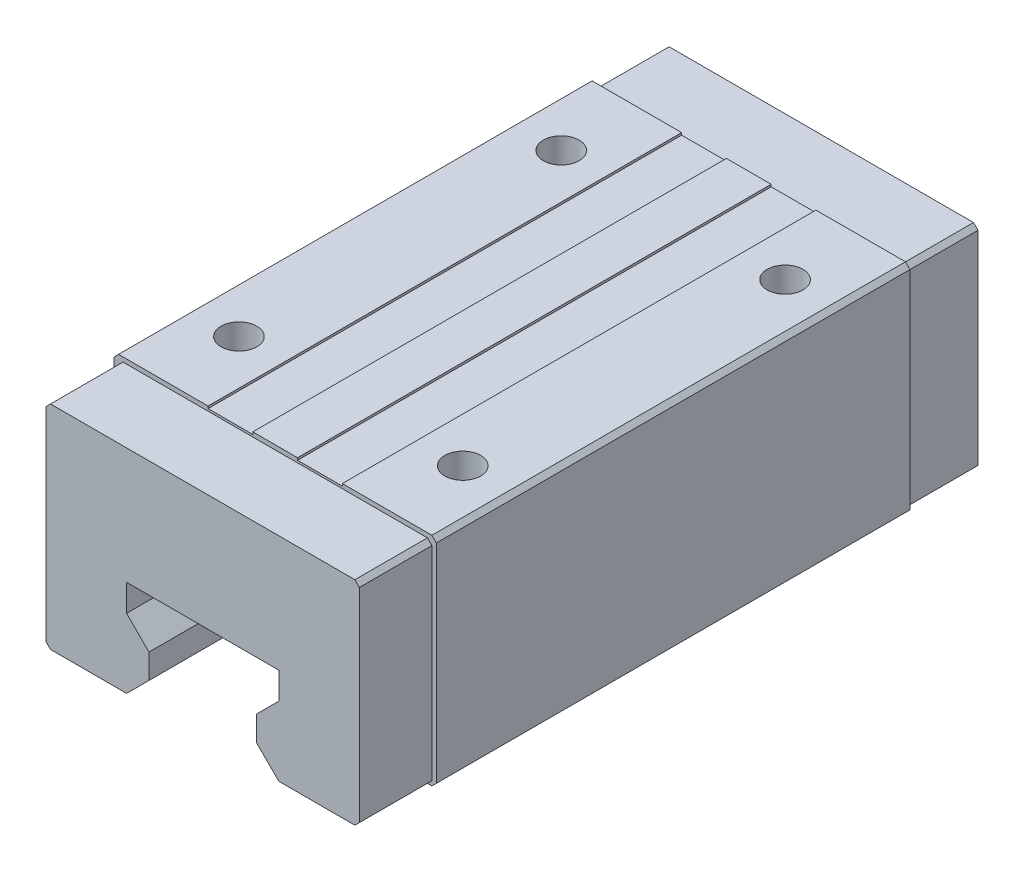
SolidWorks part; units mm, degrees
ref_plane "前视基准面" through (0, 0, 0) normal (0, 0, 1) x (1, 0, 0)
ref_plane "上视基准面" through (0, 0, 0) normal (0, 1, 0) x (1, 0, 0)
ref_plane "右视基准面" through (0, 0, 0) normal (1, 0, 0) x (0, 0, -1)
other "Configuration Table"
sketch "草图1" plane through (0, 0, 0) normal (0, 0, 1) x (1, 0, 0)
  line L0 (0, 55.4366) -> (0, -12.6403) construction
  line L1 (-35, 47.5) -> (35, 47.5)
  line L2 (35, 47.5) -> (35, 0)
  line L3 (35, 0) -> (17, 0)
  line L8 (17, 21.5) -> (-17, 21.5)
  line L13 (-35, 0) -> (-17, 0)
  line L14 (-35, 47.5) -> (-35, 0)
  line L15 (17, 15.5) -> (12, 10.5)
  line L16 (12, 10.5) -> (12, 5)
  line L17 (12, 5) -> (17, 0)
  line L19 (-12, 5) -> (-17, 0)
  line L20 (-12, 10.5) -> (-12, 5)
  line L21 (-17, 15.5) -> (-12, 10.5)
  line L22 (17, 15.5) -> (17, 21.5)
  line L23 (-17, 15.5) -> (-17, 21.5)
  point P19 (0, 21.5)
  point P25 (0, 47.5)
  dimension "D1" = 47.5
  dimension "D2" = 35
  dimension "D3" = 5
  dimension "D4" = 21.5
  dimension "D5" = 6
  dimension "D6" = 135
  dimension "D7" = 17
extrude "凸台-拉伸1" add sketch "草图1" along normal blind 138.2 contours L17 L3 L2 L1 L14 L13 L19 L20 L21 L23 L8 L22 L15 L16
ref_plane "基准面1" through (0, 0, 69.1) normal (0, 0, 1) x (1, 0, 0)
sketch "草图2" plane through (0, 0, 69.1) normal (0, 0, 1) x (1, 0, 0)
  line L0 (-36, 0) -> (-35, 0)
  line L1 (-35, 47.5) -> (-35, 0) construction
  line L2 (-36, 0) -> (-36, 48.5)
  line L3 (-36, 48.5) -> (-15, 48.5)
  line L4 (-35, 47.5) -> (35, 47.5) construction
  line L6 (-5, 48.5) -> (5, 48.5)
  line L7 (0, 0) -> (0, 45.4303) construction
  line L8 (36, 0) -> (35, 0)
  line L11 (-35, 47.5) -> (35, 47.5)
  line L12 (-35, 47.5) -> (-35, 0)
  line L13 (-15, 48.5) -> (-15, 48)
  line L14 (-15, 48) -> (-5, 48)
  line L15 (-5, 48) -> (-5, 48.5)
  line L16 (5, 48) -> (5, 48.5)
  line L17 (15, 48) -> (5, 48)
  line L18 (15, 48.5) -> (15, 48)
  line L19 (35, 47.5) -> (35, 0)
  line L20 (36, 48.5) -> (15, 48.5)
  line L21 (36, 0) -> (36, 48.5)
  line L22 (36, 0) -> (35, 0)
  point P8 (0, 48.5)
  point P13 (0, 48.5)
  point P23 (0, 47.5)
  dimension "D1" = 1
  dimension "D2" = 1
  dimension "D3" = 5
  dimension "D4" = 10
  dimension "D5" = 0.5
extrude "凸台-拉伸2" add sketch "草图2" along normal mid plane 105.8 contours L19 L11 L12 L0 L2 L3 L13 L14 L15 L6 L16 L17 L18 L20 L21 L8
sketch "草图4" plane through (0, 48.5, 0) normal (0, 1, 0) x (1, 0, 0)
  line L0 (0, 0) -> (0, -127.4396) construction
  line L1 (-42.8685, -69.1) -> (57.3984, -69.1) construction
  line L2 (-35, -138.2) -> (35, -138.2) construction
  line L3 (-35, 0) -> (35, 0) construction
  circle A0 centre (25, -33.1) radius 4
  circle A1 centre (25, -105.1) radius 4
  circle A2 centre (-25, -105.1) radius 4
  circle A3 centre (-25, -33.1) radius 4
  dimension "D1" = 8
  dimension "D2" = 25
  dimension "D3" = 72
extrude "切除-拉伸1" cut sketch "草图4" against normal blind 12
chamfer "倒角1" distance 1 angle 45 12 edges at (35, 0, 130.1) (36, 0, 69.1) (35, 0, 8.1) (-35, 47.5, 8.1) (35, 47.5, 8.1) (36, 48.5, 69.1) (35, 47.5, 130.1) (-36, 48.5, 69.1) (-35, 47.5, 130.1) (-35, 0, 8.1) (-35, 0, 130.1) (-36, 0, 69.1)
